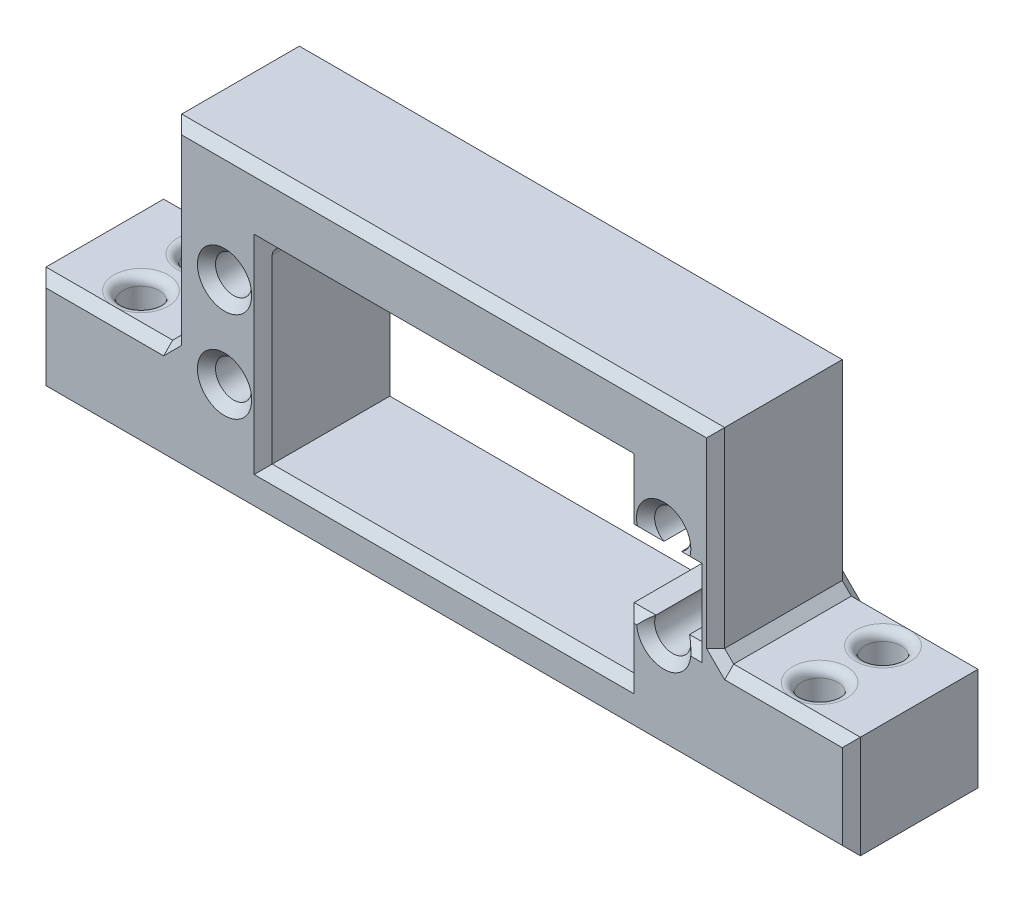
SolidWorks part; units mm, degrees
ref_plane "Front" through (0, 0, 0) normal (0, 0, 1) x (1, 0, 0)
ref_plane "Top" through (0, 0, 0) normal (0, 1, 0) x (1, 0, 0)
ref_plane "Right" through (0, 0, 0) normal (1, 0, 0) x (0, 0, -1)
sketch "Sketch1" plane through (0, 0, 0) normal (0, 0, 1) x (1, 0, 0)
  line L0 (-30, 0) -> (-30, 28.5)
  line L1 (55, 0) -> (-55, 0) construction
  line L4 (-30, 28.5) -> (30, 28.5)
  line L6 (0, -55) -> (0, 55) construction
  line L7 (20, 21) -> (-20, 21)
  line L8 (-20, 21) -> (-20, 0)
  line L9 (-20, 0) -> (-30, 0)
  line L10 (20, 0) -> (30, 0)
  line L11 (20, 21) -> (20, 0)
  line L14 (30, 0) -> (30, 28.5)
  line L15 (30, 6.3573) -> (45, 6.3573)
  line L16 (-30, 0) -> (-45, 0)
  line L17 (-30, 0) -> (-30, 6.3573)
  line L18 (-30, 6.3573) -> (-45, 6.3573)
  line L19 (-45, 0) -> (-45, 6.3573)
  line L20 (45, 0) -> (45, 6.3573)
  line L21 (30, 0) -> (45, 0)
  line L22 (30, 0) -> (30, 6.3573)
  line L24 (-45, 0) -> (45, 0)
  line L25 (-45, 0) -> (-45, -5)
  line L26 (-45, -5) -> (45, -5)
  line L27 (45, 0) -> (45, -5)
  line L28 (20, 14.25) -> (27.5, 14.25)
  line L29 (20, 14.25) -> (20, 6.75)
  line L30 (20, 6.75) -> (27.5, 6.75)
  line L31 (27.5, 14.25) -> (27.5, 6.75)
  circle A0 centre (-24.265, 16) radius 2
  circle A1 centre (-24.265, 6) radius 2
  circle A2 centre (24.265, 6) radius 2
  circle A3 centre (24.265, 16) radius 2
  point P16 (0, 21)
  point P17 (0, 28.5)
  point P35 (27.5, 10.5)
  point P36 (20, 10.5)
  dimension "D5" = 4
  dimension "D6" = 7.5
  dimension "D1" = 7.5
  dimension "D2" = 48.53
  dimension "D3" = 10
  dimension "D4" = 20
  dimension "D7" = 10
  dimension "D8" = 21
  dimension "D9" = 15
  dimension "D10" = 5
  dimension "D11" = 5
  dimension "D12" = 6
  dimension "D13" = 7.5
extrude "Boss-Extrude1" add sketch "Sketch1" along normal blind 15 contours L19 L16 L0 L18 | L10 L14 L4 L0 L9 L8 L7 L11 A2 A1 A0 A3 | L14 L21 L20 L15 | L27 L21 L10 L24 L9 L16 L25 L26 | L25 L24 L27 L26 region at (-37.5, 3.1787, 0) region at (-29.3358, 3.1787, 0) region at (0, -2.5, 0) region at (37.5, 3.1787, 0)
sketch "Sketch2" plane through (0, 6.3573, 0) normal (0, 1, 0) x (1, 0, 0)
  line L0 (-37.5, -4) -> (-37.5, -11) construction
  line L1 (0, -55) -> (0, 55) construction
  line L2 (37.5, -4) -> (37.5, -11) construction
  line L3 (0, -15) -> (0, 0) construction
  line L4 (-30, -15) -> (30, -15) construction
  circle A0 centre (-37.5, -4) radius 2
  circle A1 centre (-37.5, -11) radius 2
  circle A2 centre (37.5, -11) radius 2
  circle A3 centre (37.5, -4) radius 2
  point P15 (-37.5, -7.5)
  point P16 (0, -7.5)
  dimension "D1" = 4
  dimension "D2" = 4
  dimension "D3" = 7
  dimension "D4" = 75
extrude "Cut-Extrude1" cut sketch "Sketch2" against normal through all both and the other way through all
chamfer "Chamfer1" distance 1 angle 45 46 edges at (24.265, 18, 15) (-22.265, 16, 15) (-22.265, 6, 15) (24.265, 4, 15) (-37.5, 6.3573, 15) (-30, 17.4287, 15) (0, 28.5, 15) (30, 17.4287, 15) (37.5, 6.3573, 15) (45, 0.6787, 15) (20, 3.375, 15) (20, 17.625, 15) (0, 21, 15) (-20, 10.5, 15) (0, 0, 15) (-45, 0.6787, 15) (24.265, 18, 0) (-22.265, 16, 0) (-22.265, 6, 0) (24.265, 4, 0) (-20, 10.5, 0) (0, 21, 0) (20, 3.375, 0) (20, 17.625, 0) (0, 0, 0) (45, 0.6787, 0) (37.5, 6.3573, 0) (30, 17.4287, 0) (0, 28.5, 0) (-30, 17.4287, 0) (-37.5, 6.3573, 0) (-45, 0.6787, 0) (0, -5, 15) (0, -5, 0) (30, 6.3573, 7.5) (-30, 6.3573, 7.5) (26.8095, 6.75, 15) (21.2055, 6.75, 15) (27.5, 10.5, 15) (21.6484, 14.25, 15) (26.3666, 14.25, 15) (26.3666, 14.25, 0) (21.6484, 14.25, 0) (27.5, 10.5, 0) (21.2055, 6.75, 0) (26.8095, 6.75, 0)
fillet "Fillet1" radius 1 7 edges at (-20, 21, 7.5) (20, 21, 7.5) (39.5, -5, 11) (35.5, 6.3573, 11) (35.5, 6.3573, 4) (-35.5, 6.3573, 11) (-35.5, 6.3573, 4)
